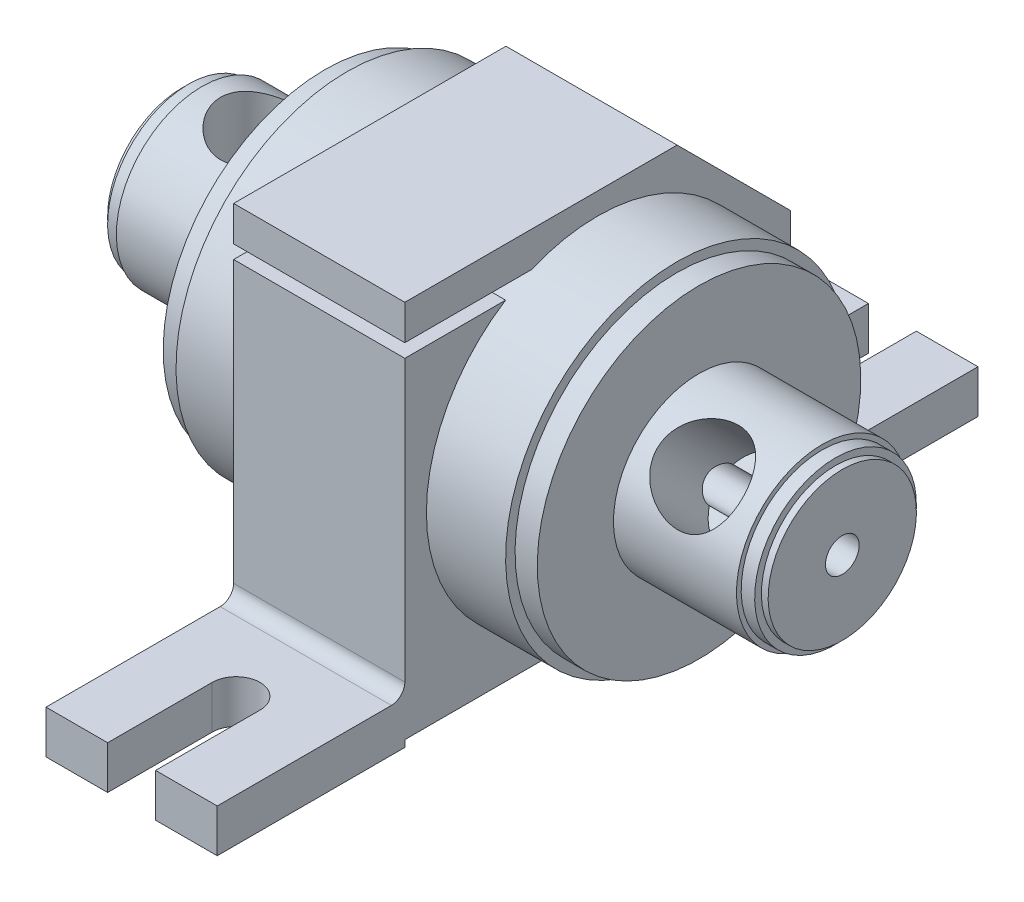
SolidWorks part; units mm, degrees
ref_plane "Front Plane" through (0, 0, 0) normal (0, 0, 1) x (1, 0, 0)
ref_plane "Top Plane" through (0, 0, 0) normal (0, 1, 0) x (1, 0, 0)
ref_plane "Right Plane" through (0, 0, 0) normal (1, 0, 0) x (0, 0, -1)
sketch "Sketch1" plane through (0, 0, 0) normal (0, 0, 1) x (1, 0, 0)
  line L0 (21.1806, 0) -> (-21.1806, 0) construction
  line L1 (-49, 2.5) -> (-49, 11)
  line L2 (-49, 11) -> (-48, 11)
  line L3 (-48, 11) -> (-48, 12)
  line L4 (-48, 12) -> (-46, 12)
  line L5 (-46, 12) -> (-46, 12.7)
  line L6 (-46, 12.7) -> (-27.75, 12.7)
  line L7 (-27.75, 12.7) -> (-27.75, 24)
  line L8 (-27.75, 24) -> (-24.45, 24)
  line L9 (-24.45, 24) -> (-24.45, 25.4)
  line L10 (-24.45, 25.4) -> (24.45, 25.4)
  line L11 (0, 25.4) -> (0, -3.4174) construction
  line L12 (-49, 2.5) -> (49, 2.5)
  line L13 (24.45, 24) -> (24.45, 25.4)
  line L14 (27.75, 24) -> (24.45, 24)
  line L15 (27.75, 12.7) -> (27.75, 24)
  line L16 (46, 12.7) -> (27.75, 12.7)
  line L17 (46, 12) -> (46, 12.7)
  line L18 (48, 12) -> (46, 12)
  line L19 (48, 11) -> (48, 12)
  line L20 (49, 11) -> (48, 11)
  line L21 (49, 2.5) -> (49, 11)
  point P4 (0, 0)
  point P20 (0, 2.5)
  dimension "D1" = 5
  dimension "D2" = 25.4
  dimension "D3" = 50.8
  dimension "D4" = 24
  dimension "D5" = 22
  dimension "D6" = 48
  dimension "D7" = 98
  dimension "D8" = 55.5
  dimension "D9" = 48.9
  dimension "D10" = 1
  dimension "D11" = 2
revolve "Revolve1" add sketch "Sketch1" angle 360 about L0
sketch "Sketch2" plane through (0, 0, 0) normal (0, 1, 0) x (1, 0, 0)
  line L0 (-51.3432, 0) -> (57.0031, 0) construction
  line L3 (-36.875, 13.6179) -> (-36.875, -13.8033) construction
  line L4 (-46, 12) -> (-46, -12) construction
  line L5 (-27.75, 12.7) -> (-27.75, -12.7) construction
  circle A0 centre (-36.875, 0) radius 6.35
  dimension "D1" = 12.7
extrude "Cut-Extrude1" cut sketch "Sketch2" along normal up to next
ref_plane "Plane1" through (0, 0, 0) normal (0, 0.7071, 0.7071) x (-1, 0, 0)
sketch "Sketch3" plane through (0, 0, 0) normal (0, 0.7071, 0.7071) x (-1, 0, 0)
  line L0 (55.1468, 0) -> (-68.1654, 0) construction
  line L1 (-36.875, -10.5033) -> (-36.875, 11.4209) construction
  line L2 (-27.75, 12.7) -> (-27.75, -12.7) construction
  line L3 (-46, 12.7) -> (-46, -12.7) construction
  circle A0 centre (-36.875, 0) radius 6.35
  dimension "D1" = 12.7
extrude "Cut-Extrude2" cut sketch "Sketch3" along normal up to next
sketch "Sketch4" plane through (0, 0, 0) normal (1, 0, 0) x (0, 0, -1)
  line L0 (0, 117.7445) -> (0, -42.5286) construction
  line L1 (-56.4369, -28.58) -> (-56.4369, -22.18)
  line L2 (-56.4369, -22.18) -> (-30.6, -22.18)
  line L3 (-28.6, -20.18) -> (-28.6, 21.42)
  line L4 (-28.6, 21.42) -> (-13.6508, 21.42)
  line L5 (-28.6, 23.42) -> (-28.6, 28.62)
  line L6 (-28.6, 28.62) -> (11.8, 28.62)
  line L7 (11.8, 28.62) -> (28.6, 11.82)
  line L8 (28.6, 11.82) -> (28.6, -20.18)
  line L9 (30.6, -22.18) -> (56.4369, -22.18)
  line L10 (56.4369, -22.18) -> (56.4369, -28.58)
  line L11 (56.4369, -28.58) -> (28.6, -28.58)
  line L12 (28.6, -28.58) -> (28.6, -27.58)
  line L13 (28.6, -27.58) -> (-28.6, -27.58)
  line L14 (-28.6, -27.58) -> (-28.6, -28.58)
  line L15 (-28.6, -28.58) -> (-56.4369, -28.58)
  line L16 (-28.6, 23.42) -> (-9.8318, 23.42)
  circle A0 centre (0, 0) radius 25.4 construction
  circle A1 centre (0, 0) radius 25.4
  arc A2 (28.6, -20.18) -> (30.6, -22.18) centre (30.6, -20.18) ccw
  arc A3 (-30.6, -22.18) -> (-28.6, -20.18) centre (-30.6, -20.18) ccw
  point P7 (0, 37.608)
  dimension "D12" = 2
  dimension "D1" = 57.2
  dimension "D2" = 1
  dimension "D3" = 57.2
  dimension "D4" = 57.2
  dimension "D5" = 27.8369
  dimension "D6" = 6.4
  dimension "D7" = 45
  dimension "D8" = 40.4
  dimension "D9" = 2
  dimension "D10" = 50
  dimension "D11" = 28.58
extrude "Boss-Extrude1" add sketch "Sketch4" along normal mid plane 25.4 contours L0 A1 L4 L3 A3 L2 L1 L15 L14 L13 | L6 L0 A1 L13 L12 L11 L10 L9 A2 L8 L7 | L0 L6 L5 L16 A1 region at (0, -11.0051, -25.9799) region at (0, 26.1941, 15.3217) region at (0, -13.2631, 27.9978)
sketch "Sketch5" plane through (0, -22.18, 0) normal (0, 1, 0) x (1, 0, 0)
  line L0 (0, 56.4369) -> (0, 40.9369) construction
  line L1 (12.7, 56.4369) -> (-12.7, 56.4369) construction
  line L2 (3.555, 56.4369) -> (3.555, 40.9369)
  line L3 (-3.555, 56.4369) -> (-3.555, 40.9369)
  line L4 (0, -56.4369) -> (0, -40.9369) construction
  line L5 (12.7, -56.4369) -> (-12.7, -56.4369) construction
  line L6 (-3.555, -56.4369) -> (-3.555, -40.9369)
  line L7 (3.555, -56.4369) -> (3.555, -40.9369)
  arc A0 (3.555, 56.4369) -> (-3.555, 56.4369) centre (0, 56.4369) ccw
  arc A1 (-3.555, 40.9369) -> (3.555, 40.9369) centre (0, 40.9369) ccw
  arc A2 (-3.555, -56.4369) -> (3.555, -56.4369) centre (0, -56.4369) ccw
  arc A3 (3.555, -40.9369) -> (-3.555, -40.9369) centre (0, -40.9369) ccw
  point P5 (0, 48.6869)
  point P10 (0, -48.6869)
  dimension "D1" = 7.11
  dimension "D2" = 15.5
extrude "Cut-Extrude3" cut sketch "Sketch5" against normal blind 25.4
sketch "Sketch6" plane through (0, 20.178, -20.242) normal (0, -0.7071, 0.7071) x (-1, 0, 0)
  line L0 (-12.7, -5.5361) -> (12.7, -5.5361) construction
  line L1 (-12.7, 25.3547) -> (-12.7, -25.4453) construction
  line L2 (12.7, -25.4453) -> (12.7, 25.3547) construction
  text T0 "→" font "Century Gothic" height in points 40
wrap "Wrap1" sketch "Sketch6" wrap type scribe source sketch "Sketch6" face at (0, 20.22, -20.2)
sketch "Sketch7" [suppressed] plane through (0, 0, 0) normal (0, 1, 0) x (1, 0, 0)
  line L0 (64.9864, 0) -> (-68.9756, 0) construction
  line L1 (49, -11) -> (49, 11) construction
  line L2 (27.75, -24) -> (49, -24)
  line L3 (27.75, -24) -> (27.75, 24)
  line L4 (27.75, 24) -> (49, 24)
  line L5 (49, -24) -> (49, 24)
  line L6 (0, -40.9369) -> (0, 40.9369) construction
  line L7 (-49, -24) -> (-49, 24)
  line L8 (-27.75, 24) -> (-49, 24)
  line L9 (-27.75, -24) -> (-27.75, 24)
  line L10 (-27.75, -24) -> (-49, -24)
extrude "Cut-Extrude4" [suppressed] cut sketch "Sketch7" against normal through all both and the other way through all
